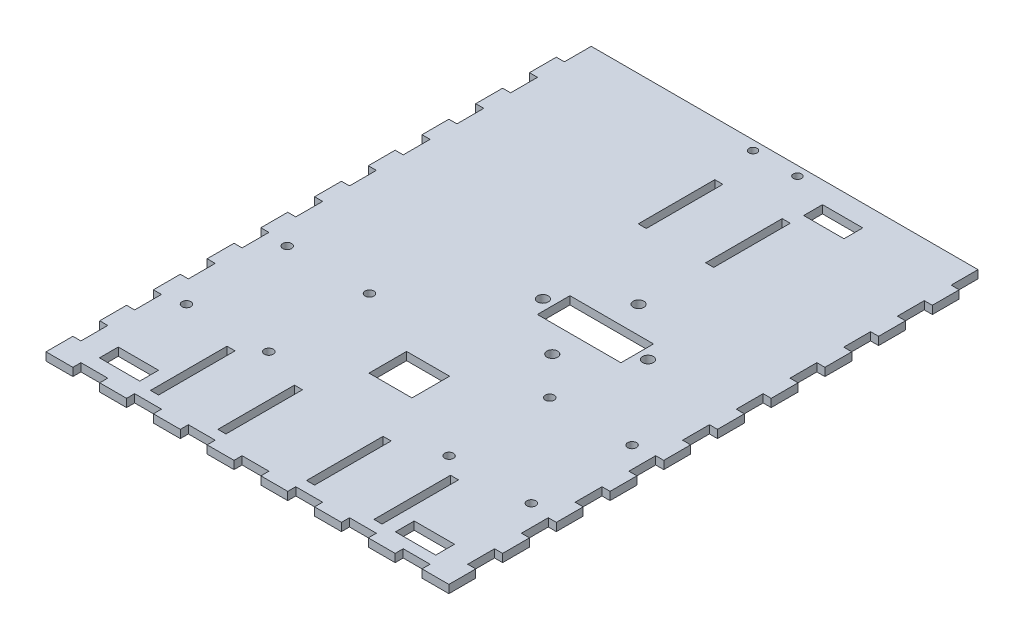
SolidWorks part; units mm, degrees
ref_plane "Plano frontal" through (0, 0, 0) normal (0, 0, 1) x (1, 0, 0)
ref_plane "Plano superior" through (0, 0, 0) normal (0, 1, 0) x (1, 0, 0)
ref_plane "Plano direito" through (0, 0, 0) normal (1, 0, 0) x (0, 0, -1)
sketch "mdfEsb" plane through (0, 0, 0) normal (0, 1, 0) x (1, 0, 0)
  line L1 (0, 0) -> (150, 0)
  line L2 (0, 0) -> (0, 200)
  line L3 (0, 200) -> (150, 200)
  line L4 (150, 0) -> (150, 200)
  dimension "D1" = 200
  dimension "D2" = 150
extrude "mdf" add sketch "mdfEsb" along normal blind 3
sketch "ldrEsb" plane through (0, 3, 0) normal (0, 1, 0) x (1, 0, 0)
  line L0 (75, 200) -> (75, 0) construction
  line L1 (31.9, 35.5) -> (34.9, 35.5)
  line L2 (31.9, 35.5) -> (31.9, 7)
  line L3 (31.9, 7) -> (34.9, 7)
  line L4 (34.9, 35.5) -> (34.9, 7)
  line L5 (57, 35.5) -> (60, 35.5)
  line L6 (57, 35.5) -> (57, 7)
  line L7 (57, 7) -> (60, 7)
  line L8 (60, 35.5) -> (60, 7)
  line L9 (0, 0) -> (150, 0) construction
  line L10 (150, 200) -> (0, 200) construction
  line L11 (90, 35.5) -> (90, 7)
  line L12 (93, 7) -> (90, 7)
  line L13 (93, 35.5) -> (93, 7)
  line L14 (93, 35.5) -> (90, 35.5)
  line L15 (115.1, 35.5) -> (115.1, 7)
  line L16 (118.1, 7) -> (115.1, 7)
  line L17 (118.1, 35.5) -> (118.1, 7)
  line L18 (118.1, 35.5) -> (115.1, 35.5)
  line L19 (72, 151.5) -> (69, 151.5)
  line L24 (94.1, 180) -> (97.1, 180)
  line L25 (94.1, 180) -> (94.1, 151.5)
  line L26 (94.1, 151.5) -> (97.1, 151.5)
  line L27 (97.1, 180) -> (97.1, 151.5)
  line L28 (69, 180) -> (69, 151.5)
  line L29 (72, 180) -> (69, 180)
  line L30 (72, 180) -> (72, 151.5)
  line L31 (123.1, 14) -> (138.1, 14)
  line L36 (26.9, 8) -> (11.9, 8)
  line L37 (26.9, 8) -> (26.9, 15)
  line L38 (26.9, 15) -> (11.9, 15)
  line L39 (11.9, 8) -> (11.9, 15)
  line L40 (97.1, 192) -> (112.1, 192)
  line L41 (97.1, 192) -> (97.1, 185)
  line L42 (97.1, 185) -> (112.1, 185)
  line L43 (112.1, 192) -> (112.1, 185)
  line L44 (138.1, 7) -> (138.1, 14)
  line L45 (123.1, 7) -> (138.1, 7)
  line L46 (123.1, 7) -> (123.1, 14)
  dimension "D1" = 28.5
  dimension "D2" = 22.1
  dimension "D3" = 3
  dimension "D4" = 3
  dimension "D5" = 15
  dimension "D6" = 7
  dimension "D7" = 28.5
  dimension "D8" = 3
  dimension "D9" = 22.1
  dimension "D10" = 20
  dimension "D11" = 15
  dimension "D12" = 7
  dimension "D13" = 5
  dimension "D14" = 3
  dimension "D15" = 7
  dimension "D16" = 7
  dimension "D17" = 28.5
  dimension "D18" = 22.1
  dimension "D19" = 15
  dimension "D20" = 3
  dimension "D21" = 3
  dimension "D22" = 5
  dimension "D23" = 7
  dimension "D24" = 15
  dimension "D26" = 3
  dimension "D27" = 15
  dimension "D28" = 8
  dimension "D29" = 5
extrude "ldrBuracos" cut sketch "ldrEsb" against normal blind 3
sketch "corEsb" plane through (0, 3, 0) normal (0, 1, 0) x (1, 0, 0)
  line L0 (75, 0) -> (75, 200) construction
  line L1 (79.44, 115.63) -> (110.56, 115.63)
  line L2 (79.44, 115.63) -> (79.44, 103.5)
  line L3 (79.44, 103.5) -> (110.56, 103.5)
  line L4 (110.56, 115.63) -> (110.56, 103.5)
  line L5 (0, 0) -> (150, 0) construction
  line L6 (150, 200) -> (0, 200) construction
  circle A0 centre (95, 125.63) radius 2
  circle A1 centre (95, 93.5) radius 2
  circle A2 centre (114.56, 109.565) radius 2
  circle A3 centre (75.44, 109.565) radius 2
  point P10 (0, 0)
  point P19 (0, 0)
  point P20 (79.44, 109.565)
  point P21 (0, 0)
  point P22 (110.56, 109.565)
  point P23 (95, 115.63)
  point P24 (0, 0)
  point P26 (95, 103.5)
  dimension "D3" = 4
  dimension "D4" = 4
  dimension "D5" = 4
  dimension "D6" = 4
  dimension "D1" = 31.12
  dimension "D2" = 12.13
  dimension "D7" = 4
  dimension "D8" = 4
  dimension "D9" = 10
  dimension "D10" = 10
  dimension "D11" = 58
  dimension "D12" = 20
extrude "corBuracos" cut sketch "corEsb" against normal blind 3
sketch "EncaixesEsb" plane through (0, 3, 0) normal (0, 1, 0) x (1, 0, 0)
  line L0 (0, 0) -> (150, 0) construction
  line L1 (10, 0) -> (20, 0)
  line L2 (10, 0) -> (10, 3)
  line L3 (10, 3) -> (20, 3)
  line L4 (20, 0) -> (20, 3)
  line L5 (0, 30) -> (0, 40)
  line L22 (0, 30) -> (3, 30)
  line L31 (0, 200) -> (0, 0) construction
  line L32 (0, 10) -> (3, 10)
  line L33 (0, 10) -> (0, 20)
  line L34 (0, 20) -> (3, 20)
  line L35 (3, 10) -> (3, 20)
  line L36 (3, 30) -> (3, 40)
  line L37 (0, 40) -> (3, 40)
  line L38 (0, 50) -> (0, 60)
  line L39 (0, 50) -> (3, 50)
  line L40 (3, 50) -> (3, 60)
  line L41 (0, 60) -> (3, 60)
  line L42 (0, 70) -> (0, 80)
  line L43 (0, 70) -> (3, 70)
  line L44 (3, 70) -> (3, 80)
  line L45 (0, 80) -> (3, 80)
  line L46 (0, 90) -> (0, 100)
  line L47 (0, 90) -> (3, 90)
  line L48 (3, 90) -> (3, 100)
  line L49 (0, 100) -> (3, 100)
  line L50 (0, 110) -> (0, 120)
  line L51 (0, 110) -> (3, 110)
  line L52 (3, 110) -> (3, 120)
  line L53 (0, 120) -> (3, 120)
  line L54 (0, 130) -> (0, 140)
  line L55 (0, 130) -> (3, 130)
  line L56 (3, 130) -> (3, 140)
  line L57 (0, 140) -> (3, 140)
  line L58 (0, 150) -> (0, 160)
  line L59 (0, 150) -> (3, 150)
  line L60 (3, 150) -> (3, 160)
  line L61 (0, 160) -> (3, 160)
  line L62 (0, 170) -> (0, 180)
  line L63 (0, 170) -> (3, 170)
  line L64 (3, 170) -> (3, 180)
  line L65 (0, 180) -> (3, 180)
  line L66 (0, 190) -> (0, 200)
  line L67 (0, 190) -> (3, 190)
  line L68 (3, 190) -> (3, 200)
  line L69 (0, 200) -> (3, 200)
  line L70 (30, 0) -> (30, 3)
  line L71 (30, 0) -> (40, 0)
  line L72 (40, 0) -> (40, 3)
  line L73 (30, 3) -> (40, 3)
  line L74 (50, 0) -> (50, 3)
  line L75 (50, 0) -> (60, 0)
  line L76 (60, 0) -> (60, 3)
  line L77 (50, 3) -> (60, 3)
  line L78 (70, 0) -> (70, 3)
  line L79 (70, 0) -> (80, 0)
  line L80 (80, 0) -> (80, 3)
  line L81 (70, 3) -> (80, 3)
  line L82 (90, 0) -> (90, 3)
  line L83 (90, 0) -> (100, 0)
  line L84 (100, 0) -> (100, 3)
  line L85 (90, 3) -> (100, 3)
  line L86 (110, 0) -> (110, 3)
  line L87 (110, 0) -> (120, 0)
  line L88 (120, 0) -> (120, 3)
  line L89 (110, 3) -> (120, 3)
  line L90 (130, 0) -> (130, 3)
  line L91 (130, 0) -> (140, 0)
  line L92 (140, 0) -> (140, 3)
  line L93 (130, 3) -> (140, 3)
  line L94 (10, 0) -> (30, 0) construction
  line L125 (147, 30) -> (147, 40)
  line L126 (147, 30) -> (150, 30)
  line L127 (147, 10) -> (150, 10)
  line L128 (147, 10) -> (147, 20)
  line L129 (147, 20) -> (150, 20)
  line L130 (150, 10) -> (150, 20)
  line L131 (150, 30) -> (150, 40)
  line L132 (147, 40) -> (150, 40)
  line L133 (147, 50) -> (147, 60)
  line L134 (147, 50) -> (150, 50)
  line L135 (150, 50) -> (150, 60)
  line L136 (147, 60) -> (150, 60)
  line L137 (147, 70) -> (147, 80)
  line L138 (147, 70) -> (150, 70)
  line L139 (150, 70) -> (150, 80)
  line L140 (147, 80) -> (150, 80)
  line L141 (147, 90) -> (147, 100)
  line L142 (147, 90) -> (150, 90)
  line L143 (150, 90) -> (150, 100)
  line L144 (147, 100) -> (150, 100)
  line L145 (147, 110) -> (147, 120)
  line L146 (147, 110) -> (150, 110)
  line L147 (150, 110) -> (150, 120)
  line L148 (147, 120) -> (150, 120)
  line L149 (147, 130) -> (147, 140)
  line L150 (147, 130) -> (150, 130)
  line L151 (150, 130) -> (150, 140)
  line L152 (147, 140) -> (150, 140)
  line L153 (147, 150) -> (147, 160)
  line L154 (147, 150) -> (150, 150)
  line L155 (150, 150) -> (150, 160)
  line L156 (147, 160) -> (150, 160)
  line L157 (147, 170) -> (147, 180)
  line L158 (147, 170) -> (150, 170)
  line L159 (150, 170) -> (150, 180)
  line L160 (147, 180) -> (150, 180)
  line L161 (147, 190) -> (147, 200)
  line L162 (147, 190) -> (150, 190)
  line L163 (150, 190) -> (150, 200)
  line L164 (147, 200) -> (150, 200)
  line L165 (150, 0) -> (150, 200) construction
  dimension "D1" = 10
  dimension "D2" = 3
  dimension "D3" = 10
  dimension "D4" = 7
  dimension "D5" = 20
  dimension "D7" = 2
  dimension "D16" = 3
  dimension "D17" = 10
  dimension "D18" = 10
  dimension "D20" = 10
  dimension "D19" = 10
extrude "Encaixe" cut sketch "EncaixesEsb" against normal blind 3
sketch "AcoplMotorEsb" plane through (0, 3, 0) normal (0, 1, 0) x (1, 0, 0)
  line L0 (75, 3) -> (75, 200) construction
  line L1 (80, 3) -> (70, 3) construction
  line L3 (118.1, 35.5) -> (115.1, 35.5) construction
  line L4 (147, 40) -> (147, 30) construction
  line L5 (147, 200) -> (3, 200) construction
  line L6 (10.8, 41.5) -> (10.8, 79) construction
  line L7 (10.8, 79) -> (10.8, 60.25) construction
  line L8 (10.8, 60.25) -> (161.2843, 60.25) construction
  line L10 (67, 53.25) -> (83, 53.25)
  line L11 (67, 53.25) -> (67, 67.25)
  line L12 (67, 67.25) -> (83, 67.25)
  line L13 (83, 53.25) -> (83, 67.25)
  line L14 (67, 53.25) -> (83, 67.25) construction
  line L15 (67, 67.25) -> (83, 53.25) construction
  circle A0 centre (108.56, 41.5) radius 1.65
  circle A1 centre (108.56, 79) radius 1.65
  circle A2 centre (139.2, 41.5) radius 1.65
  circle A3 centre (139.2, 79) radius 1.65
  circle A4 centre (10.8, 79) radius 1.65
  circle A5 centre (10.8, 41.5) radius 1.65
  circle A6 centre (41.44, 79) radius 1.65
  circle A7 centre (41.44, 41.5) radius 1.65
  point P14 (75, 60.25)
  dimension "D1" = 3.3
  dimension "D3" = 37.5
  dimension "D4" = 7.8
  dimension "D5" = 33.56
  dimension "D2" = 6
  dimension "D6" = 14
  dimension "D7" = 16
extrude "AcoplMotor" cut sketch "AcoplMotorEsb" against normal blind 3
sketch "CasterFurosEsb" plane through (0, 3, 0) normal (0, 1, 0) x (1, 0, 0)
  line L0 (75, 200) -> (75, 3) construction
  line L1 (147, 200) -> (3, 200) construction
  line L2 (80, 3) -> (70, 3) construction
  circle A0 centre (66.75, 196.5) radius 1.5
  circle A1 centre (83.25, 196.5) radius 1.5
  dimension "D1" = 3
  dimension "D2" = 3.5
  dimension "D3" = 8.25
extrude "CasterFuros" cut sketch "CasterFurosEsb" against normal blind 3
